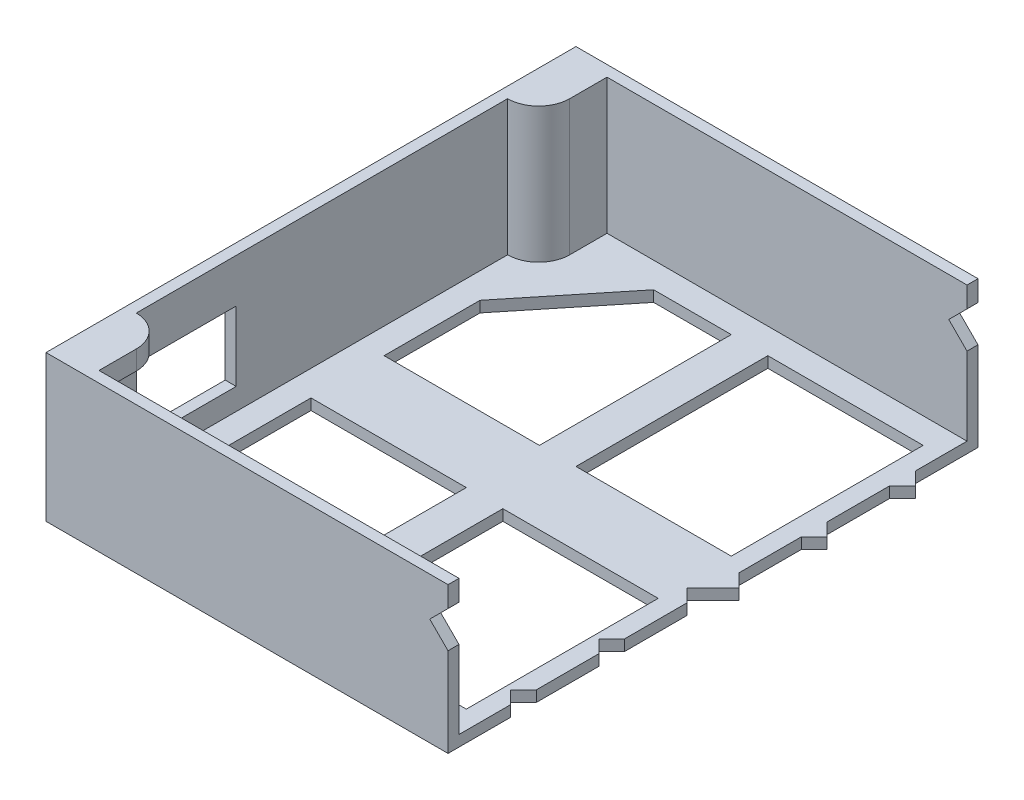
SolidWorks part; units mm, degrees
note: The reader was unsure of these and kept them because the rebuilt part matched: shared geometry of "Sketch3<6>".
ref_plane "Front Plane" through (0, 0, 0) normal (0, 0, 1) x (1, 0, 0)
ref_plane "Top Plane" through (0, 0, 0) normal (0, 1, 0) x (1, 0, 0)
ref_plane "Right Plane" through (0, 0, 0) normal (1, 0, 0) x (0, 0, -1)
sketch "Sketch1" plane through (0, 0, 0) normal (0, 1, 0) x (1, 0, 0)
  line L0 (110, 145) -> (110, 0) construction
  line L1 (0, 0) -> (220, 0)
  line L2 (0, 0) -> (0, 145)
  line L3 (0, 145) -> (220, 145)
  line L4 (220, 0) -> (220, 145)
  line L7 (10, 82.5) -> (52.5, 82.5)
  line L8 (52.5, 135) -> (52.5, 82.5)
  line L9 (62.5, 135) -> (105, 135)
  line L10 (62.5, 135) -> (62.5, 82.5)
  line L11 (62.5, 82.5) -> (105, 82.5)
  line L12 (105, 135) -> (105, 82.5)
  line L13 (110, 72.5) -> (0, 72.5) construction
  line L14 (52.5, 135) -> (62.5, 135) construction
  line L15 (62.5, 82.5) -> (62.5, 72.5) construction
  line L16 (10, 82.5) -> (10, 108.75)
  line L17 (10, 135) -> (0, 135) construction
  line L18 (10, 135) -> (10, 145) construction
  line L19 (10, 145) -> (0, 145) construction
  line L20 (0, 135) -> (0, 145) construction
  line L21 (10, 108.75) -> (31.25, 135)
  line L22 (31.25, 135) -> (52.5, 135)
  line L23 (10, 135) -> (10, 108.75) construction
  line L24 (10, 135) -> (31.25, 135) construction
  line L25 (62.5, 62.5) -> (105, 62.5)
  line L26 (105, 10) -> (105, 62.5)
  line L27 (62.5, 10) -> (105, 10)
  line L28 (62.5, 10) -> (62.5, 62.5)
  line L29 (10, 36.25) -> (31.25, 10)
  line L30 (10, 62.5) -> (10, 36.25)
  line L31 (10, 62.5) -> (52.5, 62.5)
  line L32 (52.5, 10) -> (52.5, 62.5)
  line L33 (31.25, 10) -> (52.5, 10)
  line L34 (210, 62.5) -> (210, 36.25)
  line L35 (210, 62.5) -> (167.5, 62.5)
  line L36 (167.5, 10) -> (167.5, 62.5)
  line L37 (188.75, 10) -> (167.5, 10)
  line L38 (210, 36.25) -> (188.75, 10)
  line L39 (157.5, 10) -> (157.5, 62.5)
  line L40 (157.5, 10) -> (115, 10)
  line L41 (115, 10) -> (115, 62.5)
  line L42 (157.5, 62.5) -> (115, 62.5)
  line L43 (157.5, 82.5) -> (115, 82.5)
  line L44 (115, 135) -> (115, 82.5)
  line L45 (157.5, 135) -> (115, 135)
  line L46 (157.5, 135) -> (157.5, 82.5)
  line L47 (210, 108.75) -> (188.75, 135)
  line L48 (210, 82.5) -> (210, 108.75)
  line L49 (210, 82.5) -> (167.5, 82.5)
  line L50 (167.5, 135) -> (167.5, 82.5)
  line L51 (188.75, 135) -> (167.5, 135)
  point P23 (31.25, 82.5)
  point P25 (52.5, 108.75)
  dimension "D1" = 145
  dimension "D2" = 220
  dimension "D3" = 10
  dimension "D4" = 10
  dimension "D5" = 5
  dimension "D6" = 10
extrude "Boss-Extrude1" add sketch "Sketch1" along normal blind 3
sketch "Sketch2" plane through (0, 3, 0) normal (0, 1, 0) x (1, 0, 0)
  line L9 (0, 0) -> (0, 145)
  line L10 (0, 72.5) -> (3, 72.5) construction
  line L11 (3, 123.3) -> (3, 21.7)
  line L12 (11.5, 13.2) -> (11.5, 3)
  line L13 (0, 145) -> (0, 0) construction
  line L14 (0, 0) -> (220, 0) construction
  line L18 (11.5, 3) -> (208.5, 3)
  line L19 (110, 3) -> (110, 0) construction
  line L24 (220, 0) -> (0, 0)
  line L25 (110, 142) -> (110, 145) construction
  line L26 (220, 145) -> (0, 145)
  line L27 (11.5, 142) -> (208.5, 142)
  line L28 (11.5, 131.8) -> (11.5, 142)
  line L29 (220, 72.5) -> (217, 72.5) construction
  line L30 (208.5, 131.8) -> (208.5, 142)
  line L31 (208.5, 13.2) -> (208.5, 3)
  line L32 (217, 123.3) -> (217, 21.7)
  line L33 (220, 0) -> (220, 145)
  arc A4 (3, 21.7) -> (11.5, 13.2) centre (3, 13.2) cw
  arc A5 (3, 123.3) -> (11.5, 131.8) centre (3, 131.8) ccw
  arc A6 (217, 123.3) -> (208.5, 131.8) centre (217, 131.8) cw
  arc A7 (217, 21.7) -> (208.5, 13.2) centre (217, 13.2) ccw
  point P21 (0, 72.5)
  point P24 (110, 0)
  dimension "D1" = 3
  dimension "D2" = 8.5
  dimension "D3" = 18.7
extrude "Boss-Extrude2" add sketch "Sketch2" along direction (0, -1, 0) on the side of the normal offset from surface (37 mm away) 40
sketch "Sketch3" plane through (3, 0, 0) normal (-1, 0, 0) x (0, 0, 1)
  line L0 (-3, 40) -> (-3, 3) construction
  line L1 (0, 0) -> (-3, 0) construction
  line L2 (0, 0) -> (0, 3) construction
  line L3 (0, 3) -> (-3, 3) construction
  line L4 (-3, 0) -> (-3, 3) construction
  line L5 (-3, 3) -> (-56.975, 3)
  line L6 (-3, 3) -> (-3, 34.75)
  line L7 (-3, 34.75) -> (-56.975, 34.75)
  line L8 (-56.975, 3) -> (-56.975, 34.75)
  line L9 (-123.3, 3) -> (-21.7, 3) construction
  line L10 (-145, 3) -> (-3, 3) construction
  line L11 (-3, 40) -> (-3, 3) construction
  line L12 (-145, 40) -> (-145, 0) construction
  line L14 (-49.0375, 28.0031) -> (-21.2562, 28.0031)
  line L15 (-49.0375, 28.0031) -> (-49.0375, 8.9531)
  line L16 (-49.0375, 8.9531) -> (-21.2562, 8.9531)
  line L17 (-21.2562, 28.0031) -> (-21.2562, 8.9531)
  line M28 (-21.7, 40) -> (-21.7, 3)
  dimension "D1" = 53.975
  dimension "D2" = 31.75
  dimension "D3" = 27.7812
  dimension "D4" = 19.05
  dimension "D5" = 7.9375
  dimension "D6" = 6.7469
extrude "Cut-Extrude1" cut sketch "Sketch3" along normal up to surface (3 mm away) contours L16 L15 L14 M28 | L8 L7 L6 L5
extrude "Cut-Extrude2" cut sketch "Sketch3<6>" against normal up to surface (8.5 mm away) contours L7 L8 L5 L6 up to face at (11.5, 21.5, -8.1)
sketch "Sketch3<6>" plane through (3, 0, 0) normal (-1, 0, 0) x (0, 0, 1) same geometry as "Sketch3"
sketch "Sketch7" plane through (0, 0, 0) normal (0, 0, 1) x (1, 0, 0)
  line L0 (110, 40) -> (110, 34.3333)
  line L1 (220, 40) -> (0, 40) construction
  line L2 (110, 34.3333) -> (105, 29.3333)
  line L3 (105, 29.3333) -> (110, 24.3333)
  line L4 (110, 24.3333) -> (110, 18.6667)
  line L7 (110, 8.6667) -> (110, 3)
  line L8 (110, 3) -> (220, 3)
  line L9 (220, 40) -> (220, 0) construction
  line L10 (220, 3) -> (220, 40)
  line L11 (220, 40) -> (110, 40)
  line L12 (0, 0) -> (220, 0) construction
  line L13 (110, 8.6667) -> (115, 13.6667)
  line L14 (115, 13.6667) -> (110, 18.6667)
  point P16 (220, 21.5)
  point P17 (110, 21.5)
  dimension "D1" = 3
  dimension "D2" = 5
  dimension "D3" = 10
extrude "Cut-Extrude3" cut sketch "Sketch7" against normal through all both and the other way through all
sketch "Sketch8" plane through (0, 3, 0) normal (0, 1, 0) x (1, 0, 0)
  line L0 (110, 145) -> (220, 145)
  line L1 (220, 145) -> (220, 0)
  line L2 (220, 0) -> (110, 0)
  line L3 (110, 0) -> (110, 17.0956)
  line L4 (110, 17.0956) -> (106.4645, 20.6311)
  line L5 (106.4645, 20.6311) -> (110, 24.1667)
  line L6 (110, 24.1667) -> (110, 41.2623)
  line L7 (110, 41.2623) -> (106.4645, 44.7978)
  line L8 (106.4645, 44.7978) -> (110, 48.3333)
  line L11 (110, 65.4289) -> (106.4645, 68.9645)
  line L12 (106.4645, 68.9645) -> (113.5355, 76.0355)
  line L13 (113.5355, 76.0355) -> (110, 79.5711)
  line L14 (110, 79.5711) -> (110, 96.6667)
  line L15 (110, 96.6667) -> (113.5355, 100.2022)
  line L16 (113.5355, 100.2022) -> (110, 103.7377)
  line L17 (110, 103.7377) -> (110, 120.8333)
  line L18 (110, 120.8333) -> (113.5355, 124.3689)
  line L19 (113.5355, 124.3689) -> (110, 127.9044)
  line L20 (110, 127.9044) -> (110, 145)
  line L21 (110, 65.4289) -> (110, 48.3333)
  line L22 (62.5, 82.5) -> (157.5, 62.5) construction
  point P31 (113.5355, 100.3199)
  point P32 (113.5355, 107.5368)
  point P33 (106.4645, 46.3097)
  point P34 (106.4645, 25.0812)
  point P35 (106.4645, 25.0812)
  point P36 (106.4645, 25.0812)
  point P37 (0, 0)
  point P38 (0, 0)
  point P39 (110, 15.347)
  point P40 (113.5355, 76.5085)
  dimension "D1" = 5
extrude "Cut-Extrude4" cut sketch "Sketch8" against normal through all both and the other way through all
